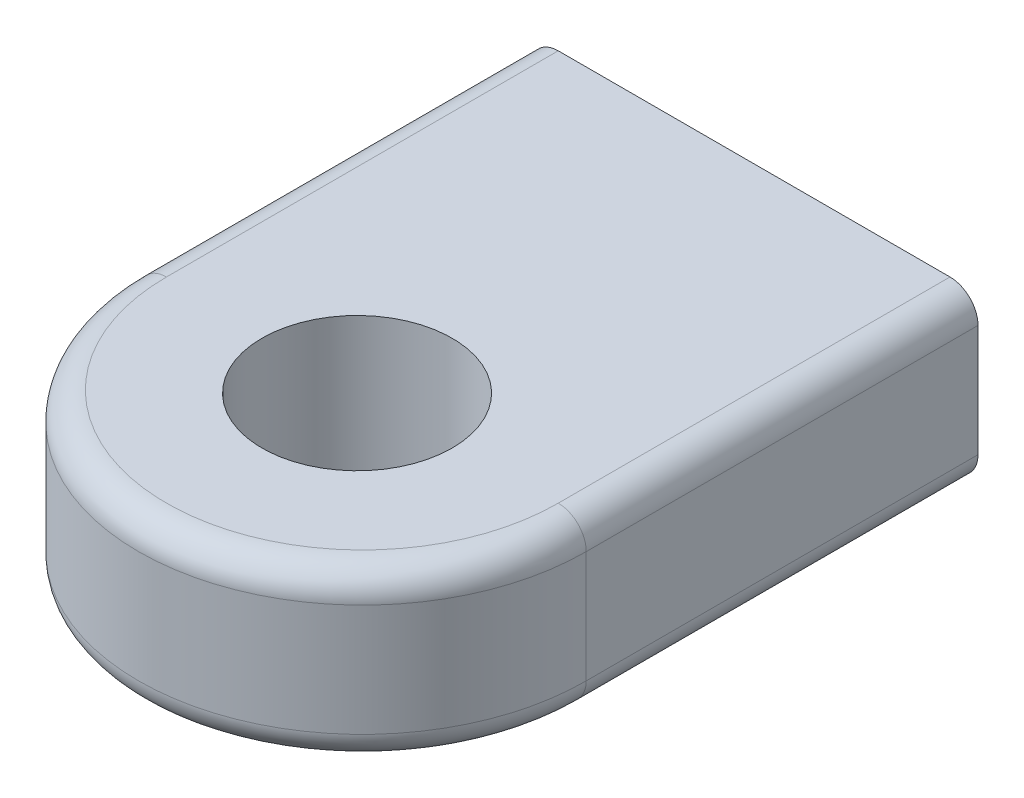
SolidWorks part; units mm, degrees
ref_plane "Front Plane" through (0, 0, 0) normal (0, 0, 1) x (1, 0, 0)
ref_plane "Top Plane" through (0, 0, 0) normal (0, 1, 0) x (1, 0, 0)
ref_plane "Right Plane" through (0, 0, 0) normal (1, 0, 0) x (0, 0, -1)
sketch "Sketch1" plane through (0, 0, 0) normal (0, 0, 1) x (1, 0, 0)
  line L1 (40, 30) -> (-40, 30)
  line L2 (40, 30) -> (40, 0)
  line L3 (40, 0) -> (-40, 0)
  line L4 (-40, 30) -> (-40, 0)
  point P4 (0, 0)
  dimension "D1" = 80
  dimension "D2" = 30
extrude "Boss-Extrude1" add sketch "Sketch1" along normal blind 110
fillet "Fillet1" 2 edges at (40, 15, 110) (-40, 15, 110) type full round first side face at (40, 15, 55) second side face at (-40, 15, 55) middle face at (0, 15, 110)
fillet "Fillet2" radius 5 6 edges at (40, 0, 35) (-40, 0, 35) (-40, 30, 35) (40, 30, 35) (0, 0, 110) (0, 30, 110)
sketch "Sketch2" plane through (0, 0, 0) normal (0, -1, 0) x (1, 0, 0)
  circle A0 centre (0, 70.95) radius 17
  dimension "D1" = 34
  dimension "D2" = 70.95
extrude "Cut-Extrude1" cut sketch "Sketch2" against normal up to next
